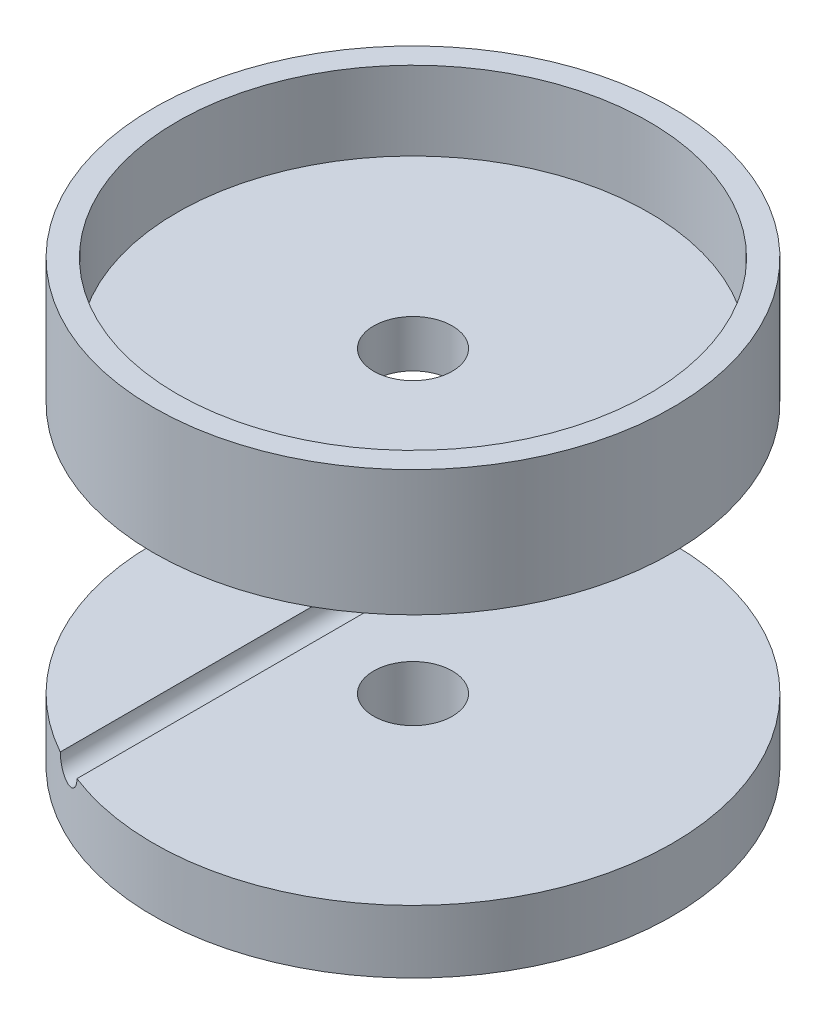
SolidWorks part; units mm, degrees
ref_plane "Piano frontale" through (0, 0, 0) normal (0, 0, 1) x (1, 0, 0)
ref_plane "Piano superiore" through (0, 0, 0) normal (0, 1, 0) x (1, 0, 0)
ref_plane "Piano destro" through (0, 0, 0) normal (1, 0, 0) x (0, 0, -1)
sketch "Schizzo1" plane through (0, 0, 0) normal (0, 1, 0) x (1, 0, 0)
  circle A0 centre (0, 0) radius 15
  circle A1 centre (0, 0) radius 16.5
  circle A2 centre (0, 0) radius 2.5
  dimension "D1" = 30
  dimension "D2" = 33
  dimension "D3" = 5
extrude "Estrusione-Estrusione1" add sketch "Schizzo1" along normal blind 3 contours A0 A2 region at (-14.5757, 0, 0)
extrude "Estrusione-Estrusione2" add sketch "Schizzo1<5>" along normal blind 8 contours A1 A0 region at (-16.0333, 0, 0)
sketch "Schizzo1<5>" plane through (0, 0, 0) normal (0, 1, 0) x (1, 0, 0) same geometry as "Schizzo1"
ref_plane "Piano1" through (0, -20, 0) normal (0, -1, 0) x (-1, 0, 0)
sketch "Schizzo4" plane through (0, -20, 0) normal (0, -1, 0) x (-1, 0, 0)
  circle A0 centre (0, 0) radius 16.5
  circle A1 centre (0, 0) radius 2.5
extrude "Estrusione-Estrusione3" add sketch "Schizzo4" against normal blind 4 separate body
sketch "Schizzo5" plane through (0, 0, 0) normal (0, 0, 1) x (1, 0, 0)
  line L0 (16.5, -16) -> (-16.5, -16) construction
  line L1 (-2.5, -16) -> (-2.5, -20) construction
  circle A0 centre (-7, -16) radius 1
  point P2 (-9.057, -16)
  dimension "D1" = 2
  dimension "D2" = 4.5
extrude "Taglio-Estrusione1" cut sketch "Schizzo5" against normal through all both and the other way through all
